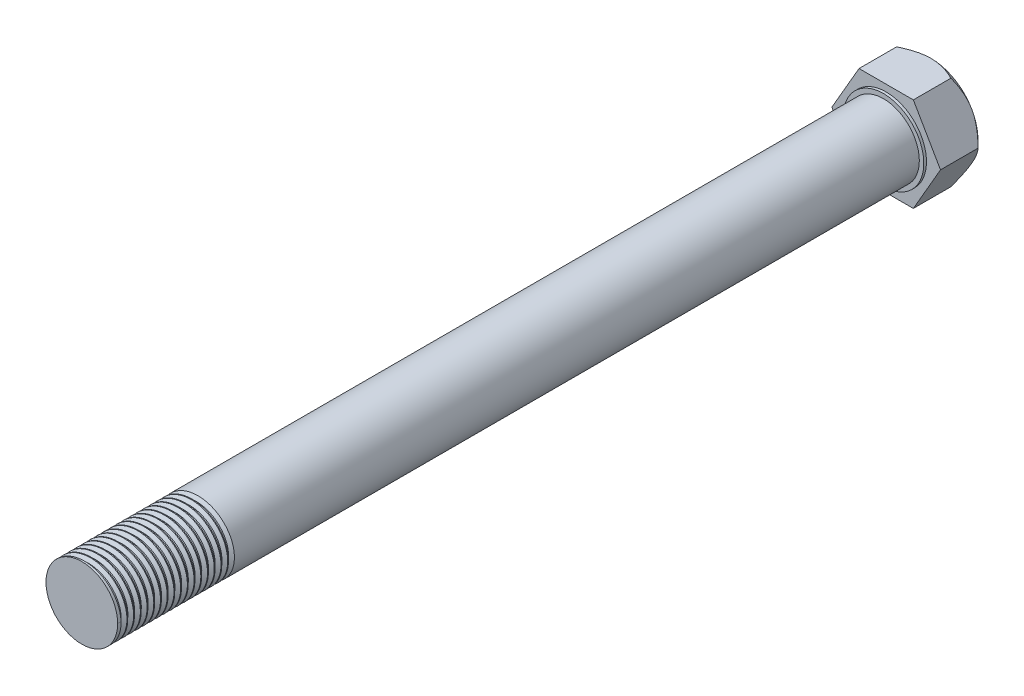
SolidWorks part; units mm, degrees
ref_plane "Front Plane" through (0, 0, 0) normal (0, 0, 1) x (1, 0, 0)
ref_plane "Top Plane" through (0, 0, 0) normal (0, 1, 0) x (1, 0, 0)
ref_plane "Right Plane" through (0, 0, 0) normal (1, 0, 0) x (0, 0, -1)
sketch "Sketch1" plane through (0, 0, 0) normal (0, 0, 1) x (1, 0, 0)
  circle A0 centre (0, 0) radius 8
  dimension "D1" = 16
extrude "Boss-Extrude1" add sketch "Sketch1" along normal blind 102 and the other way blind 77
ref_plane "Plane1" [suppressed] through (0, 0, -88) normal (0, 0, -1) x (-1, 0, 0)
sketch "Sketch2" [suppressed] plane through (0, 0, -88) normal (0, 0, -1) x (-1, 0, 0)
  line L1 (-7.5, 7.5) -> (7.5, 7.5)
  line L2 (-7.5, 7.5) -> (-7.5, -7.5)
  line L3 (-7.5, -7.5) -> (7.5, -7.5)
  line L4 (7.5, 7.5) -> (7.5, -7.5)
  line L5 (-7.5, 7.5) -> (7.5, -7.5) construction
  line L6 (-7.5, -7.5) -> (7.5, 7.5) construction
  point P0 (0, 0)
  dimension "D1" = 15
thread "Thread1" pitch 1.5 method cut profile "Thread Profile1" start angle 0, offset 0, length 25, pitch 1.5, diameter 16
ref_plane "Plane2" through (-8, 0, 102) normal (0, -1, 0) x (-1, 0, 0)
sketch "Thread Profile1" plane through (-8, 0, 102) normal (0, -1, 0) x (-1, 0, 0)
  line L0 (0, 0) -> (0, 1.5) construction
  line L11 (0, 0) -> (0, 1.3125)
  line L12 (0, 1.3125) -> (-0.8119, 0.8437)
  line L13 (-0.8119, 0.8437) -> (-0.8119, 0.4687)
  line L15 (-0.8119, 0.4687) -> (0, 0)
  line L17 (-0.8119, 0.6562) -> (0, 0.6562) construction
  point P2 (0, 0)
  dimension "Pitch" = 1.5
  dimension "Profile_Angle" = 60
  dimension "Profile_Land" = 0.375
  dimension "Profile_Height" = 0.8119
sketch "Sketch3" [suppressed] plane through (0, 0, -83) normal (0, 0, -1) x (-1, 0, 0)
  line L1 (12.1244, 0) -> (6.0622, 10.5)
  line L2 (6.0622, 10.5) -> (-6.0622, 10.5)
  line L3 (-6.0622, 10.5) -> (-12.1244, 0)
  line L4 (-12.1244, 0) -> (-6.0622, -10.5)
  line L5 (-6.0622, -10.5) -> (6.0622, -10.5)
  line L6 (6.0622, -10.5) -> (12.1244, 0)
  circle A1 centre (0, 0) radius 10.5 construction
  dimension "D1" = 21
extrude "Boss-Extrude3" [suppressed] add sketch "Sketch3" along normal blind 10
sketch "Sketch4" plane through (0, 0, -77) normal (0, 0, -1) x (-1, 0, 0)
  circle A0 centre (0, 0) radius 9
  dimension "D1" = 18
extrude "Boss-Extrude4" add sketch "Sketch4" along normal blind 0.6
sketch "Sketch5" plane through (0, 0, -77.6) normal (0, 0, -1) x (-1, 0, 0)
  line L1 (12.1244, 0) -> (6.0622, 10.5)
  line L2 (6.0622, 10.5) -> (-6.0622, 10.5)
  line L3 (-6.0622, 10.5) -> (-12.1244, 0)
  line L4 (-12.1244, 0) -> (-6.0622, -10.5)
  line L5 (-6.0622, -10.5) -> (6.0622, -10.5)
  line L6 (6.0622, -10.5) -> (12.1244, 0)
  circle A0 centre (0, 0) radius 10.5 construction
  dimension "D1" = 21
extrude "Boss-Extrude5" add sketch "Sketch5" along normal blind 10
sketch "Sketch6" plane through (0, 0, -87.6) normal (0, 0, -1) x (-1, 0, 0)
  circle A0 centre (0, 0) radius 10.5
  dimension "D1" = 21
extrude "Cut-Extrude1" cut sketch "Sketch6" against normal blind 10 draft 45 flip side to cut
